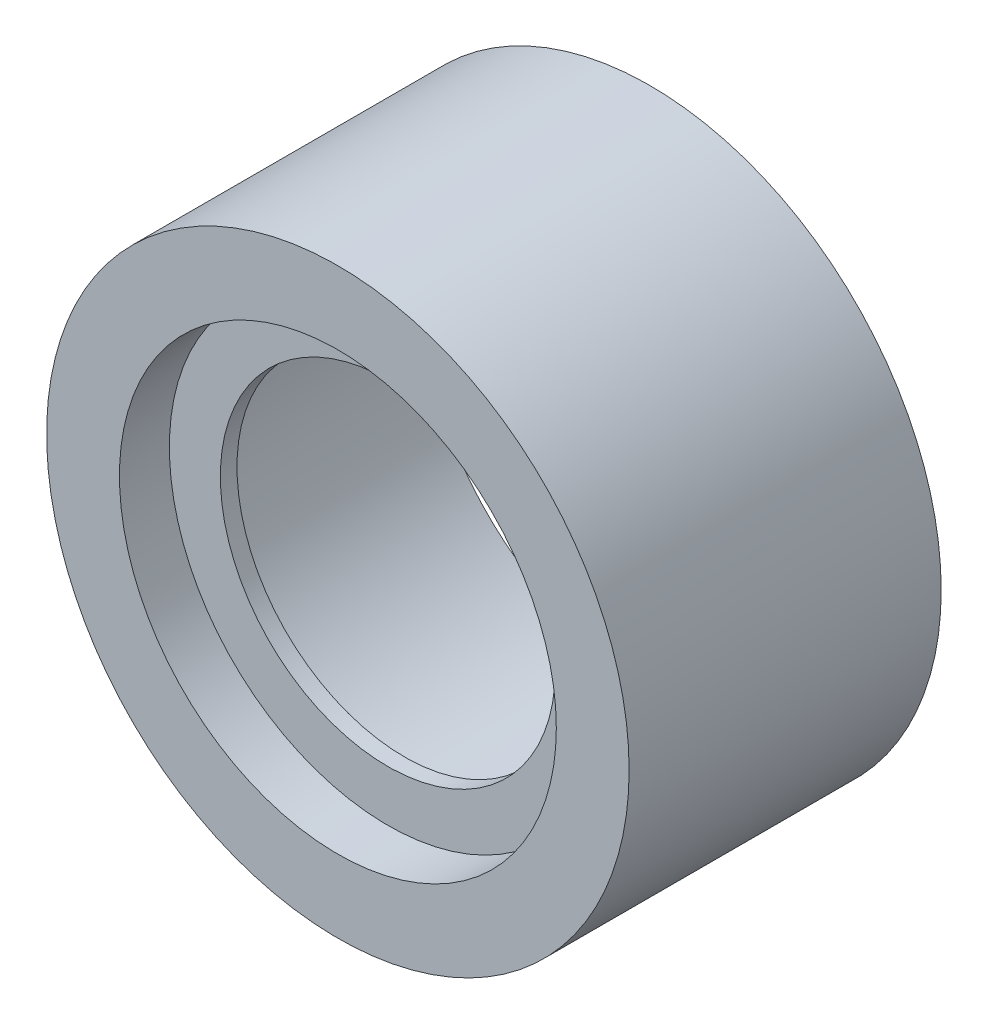
SolidWorks part; units mm, degrees
ref_plane "Front Plane" through (0, 0, 0) normal (0, 0, 1) x (1, 0, 0)
ref_plane "Top Plane" through (0, 0, 0) normal (0, 1, 0) x (1, 0, 0)
ref_plane "Right Plane" through (0, 0, 0) normal (1, 0, 0) x (0, 0, -1)
sketch "Sketch1" plane through (0, 0, 0) normal (1, 0, 0) x (0, 0, -1)
  line L0 (-84.7958, 52.5) -> (-72.7958, 52.5)
  line L1 (-73.3513, 52.5) -> (-74.0979, 52.5) construction
  line L3 (-50.0958, 55) -> (-67.2958, 55) construction
  line L4 (-84.7958, 52.5) -> (-84.7958, 70)
  line L5 (-84.7958, 70) -> (-9.7958, 70)
  line L6 (-72.7958, -51.9444) -> (-72.7958, 51.9445) construction
  line L7 (-72.7958, 52.5) -> (-72.7958, 40.25)
  line L8 (-72.7958, -48.3333) -> (-72.7958, 48.3333) construction
  line L9 (-72.7958, 40.25) -> (-68.7958, 40.25)
  line L10 (-68.7958, 53.5) -> (-68.7958, -53.5) construction
  line L11 (-68.7958, 40.25) -> (-68.7958, 55)
  line L12 (-68.7958, 55) -> (-9.7958, 55)
  line L14 (-9.7958, 70) -> (-9.7958, 55)
  line L15 (-68.7958, 40) -> (-82.7958, 40) construction
  line L16 (174.1864, 0) -> (-154.8488, 0) construction
  line L17 (-82.7958, 51.3889) -> (-82.7958, -51.3889) construction
  line L18 (-163.8227, 0) -> (139.4858, 0) construction
  dimension "D1" = 0.25
  dimension "D2" = 70
  dimension "D3" = 75
  dimension "D4" = 2
revolve "Revolve1" add sketch "Sketch1" angle 360 about L18
sketch "Sketch2" plane through (0, 0, 9.7958) normal (0, 0, -1) x (-1, 0, 0)
  line L0 (0, 62.5) -> (0, -62.5) construction
  circle A0 centre (0, 0) radius 62.5 construction
  circle A1 centre (0, 62.5) radius 4
  circle A2 centre (0, -62.5) radius 4
  dimension "D1" = 125
  dimension "D2" = 8
extrude "Cut-Extrude1" cut sketch "Sketch2" against normal blind 10
sketch "Sketch3" plane through (0, 0, 9.7958) normal (0, 0, -1) x (-1, 0, 0)
  line L0 (0, 70) -> (0, -70) construction
  line L1 (0, 70) -> (0, 55) construction
  line L2 (0, 52.5) -> (0, 70) construction
  line L3 (-44.1942, 44.1942) -> (0, 0) construction
  line L4 (0, 0) -> (-44.1942, -44.1942) construction
  line L5 (62.5, 0) -> (-62.5, 0) construction
  line L6 (0, 0) -> (44.1942, -44.1942) construction
  line L7 (44.1942, 44.1942) -> (0, 0) construction
  circle A0 centre (0, 0) radius 62.5 construction
  circle A1 centre (0, 0) radius 70 construction
  point P12 (-44.1942, 44.1942)
  point P13 (44.1942, -44.1942)
  point P14 (-62.5, 0)
  point P15 (44.1942, 44.1942)
  point P16 (-44.1942, -44.1942)
  point P17 (62.5, 0)
  dimension "D1" = 125
  dimension "D3" = 45
  dimension "D2" = 45
hole_wizard "M8x1.25 Tapped Hole1" positions "Sketch3" profile "Sketch4" tap size "M8x1.25" standard "ANSI Metric"
sketch "Sketch4" plane through (-62.5, 0, 9.7958) normal (1, 0, 0) x (0, 1, 0)
  line L0 (0, 0) -> (0, 12.0429)
  line L1 (0, 12.0429) -> (3.4, 10)
  line L2 (3.4, 10) -> (3.4, 0)
  line L5 (3.4, 0) -> (0, 0)
  line L10 (0, 12.0429) -> (-3.4, 10) construction
  line L11 (0, -6.35) -> (0, 107.95) construction
  dimension "Tap Drill Dia." = 6.8
  dimension "Tap Drill Depth" = 10
  dimension "Drill Angle" = 118
cosmetic thread "Hole Thread1"
cosmetic thread "Hole Thread2"
cosmetic thread "Hole Thread3"
cosmetic thread "Hole Thread4"
cosmetic thread "Hole Thread5"
cosmetic thread "Hole Thread6"
